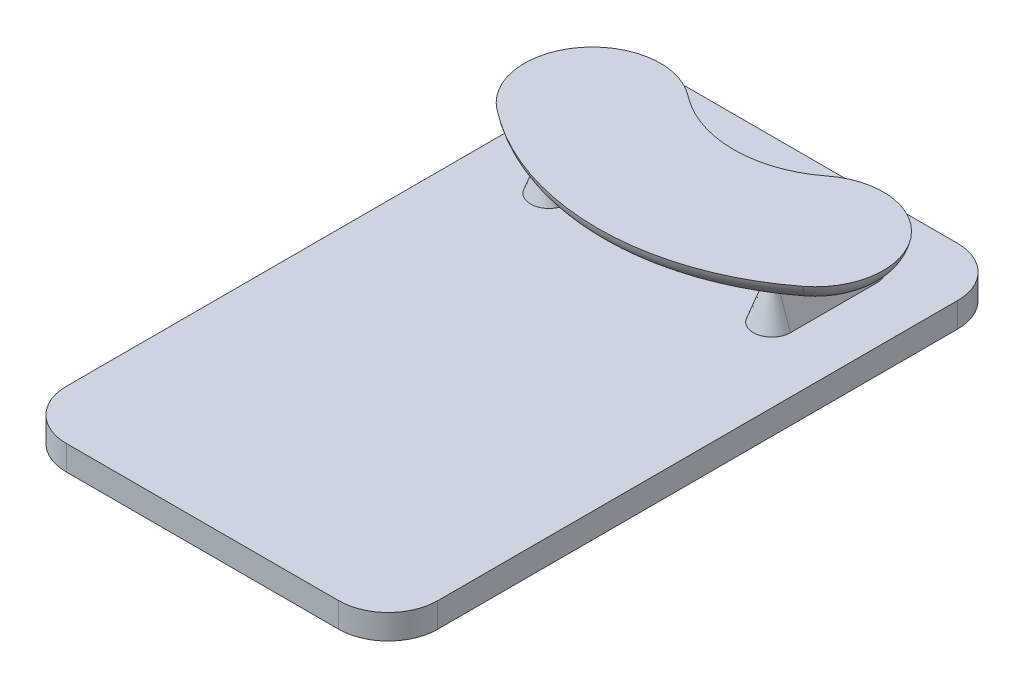
SolidWorks part; units mm, degrees
ref_plane "Plano frontal" through (0, 0, 0) normal (0, 0, 1) x (1, 0, 0)
ref_plane "Plano superior" through (0, 0, 0) normal (0, 1, 0) x (1, 0, 0)
ref_plane "Plano direito" through (0, 0, 0) normal (1, 0, 0) x (0, 0, -1)
sketch "Esboço1" plane through (0, 0, 0) normal (0, 1, 0) x (1, 0, 0)
  line L1 (-88.9739, 86.5116) -> (211.0261, 86.5116)
  line L2 (-88.9739, 86.5116) -> (-88.9739, -413.4884)
  line L3 (-88.9739, -413.4884) -> (211.0261, -413.4884)
  line L4 (211.0261, 86.5116) -> (211.0261, -413.4884)
  dimension "D1" = 500
  dimension "D2" = 300
extrude "Ressalto-extrusão1" add sketch "Esboço1" along normal blind 20
fillet "Filete2" radius 40 1 edges at (211.0261, 10, -86.5116) type face fillet first side face at (211.0261, 10, 163.4884) second side face at (61.0261, 10, -86.5116)
fillet "Filete3" radius 40 1 edges at (-88.9739, 10, -86.5116) type face fillet first side face at (41.0261, 10, -86.5116) second side face at (-88.9739, 10, 163.4884)
fillet "Filete4" radius 40 1 edges at (-88.9739, 10, 413.4884) type face fillet first side face at (-88.9739, 10, 183.4884) second side face at (61.0261, 10, 413.4884)
fillet "Filete5" radius 40 1 edges at (211.0261, 10, 413.4884) type face fillet first side face at (81.0261, 10, 413.4884) second side face at (211.0261, 10, 183.4884)
sketch "Esboço2" plane through (0, 20, 0) normal (0, 1, 0) x (1, 0, 0)
  line L0 (-28.9739, 26.5116) -> (-28.9739, -43.4884) construction
  line L1 (-13.9739, 26.5116) -> (-13.9739, -43.4884)
  line L2 (-43.9739, 26.5116) -> (-43.9739, -43.4884)
  line L3 (151.0261, 26.5116) -> (151.0261, -43.4884) construction
  line L4 (166.0261, 26.5116) -> (166.0261, -43.4884)
  line L5 (136.0261, 26.5116) -> (136.0261, -43.4884)
  line L7 (171.0261, 86.5116) -> (-48.9739, 86.5116) construction
  line L10 (211.0261, -373.4884) -> (211.0261, 46.5116) construction
  line L11 (-88.9739, 46.5116) -> (-88.9739, -373.4884) construction
  arc A0 (-13.9739, 26.5116) -> (-43.9739, 26.5116) centre (-28.9739, 26.5116) ccw
  arc A1 (-43.9739, -43.4884) -> (-13.9739, -43.4884) centre (-28.9739, -43.4884) ccw
  arc A2 (166.0261, 26.5116) -> (136.0261, 26.5116) centre (151.0261, 26.5116) ccw
  arc A3 (136.0261, -43.4884) -> (166.0261, -43.4884) centre (151.0261, -43.4884) ccw
  point P2 (-28.9739, -8.4884)
  point P9 (151.0261, -8.4884)
  point P14 (0, 0)
  dimension "D7" = 15
  dimension "D8" = 15
  dimension "D1" = 60
  dimension "D2" = 60
  dimension "D3" = 70
  dimension "D4" = 70
  dimension "D5" = 60
  dimension "D6" = 60
sketch3d "3DSketch1"
extrude "Ressalto-extrusão2" add sketch "Esboço2" along normal blind 30 draft 20
sketch "Esboço56" plane through (0, 50, 0) normal (0, 1, 0) x (1, 0, 0)
  line L4 (155.107, -43.4884) -> (155.107, 26.5116) construction
  line L5 (-33.0548, 26.5116) -> (-33.0548, -43.4884) construction
  arc A0 (151.027, -8.4876) -> (-28.9748, -8.4893) centre (61.0249, 107.161) cw construction
  arc A5 (-62.7531, -51.8947) -> (184.8061, -51.8923) centre (61.0249, 107.161) ccw
  arc A6 (4.8035, 34.916) -> (117.2478, 34.9172) centre (61.0249, 107.161) ccw
  arc A7 (4.8035, 34.916) -> (-62.7531, -51.8947) centre (-28.9748, -8.4893) ccw
  arc A8 (184.8061, -51.8923) -> (117.2478, 34.9172) centre (151.027, -8.4876) ccw
  arc A9 (-33.0548, -43.4884) -> (-24.893, -43.4884) centre (-28.9739, -43.4884) ccw construction
  arc A10 (155.107, 26.5116) -> (146.9452, 26.5116) centre (151.0261, 26.5116) ccw construction
  point P3 (61.0264, -39.3823)
  point P16 (-28.9739, -47.5693)
  point P20 (151.0261, 30.5924)
  dimension "D5" = 55
  dimension "D1" = 4.08
  dimension "D2" = 4.08
  dimension "D3" = 39.08
  dimension "D4" = 39.08
extrude "Ressalto-extrusão3" add sketch "Esboço56" along normal blind 16 contours A8 A6 A7 A5
fillet "Filete7" radius 20 4 edges at (61.0258, 50, -15.6177) (194.4317, 50, -25.2916) (61.0269, 50, 94.3823) (-72.3802, 50, -25.289)
